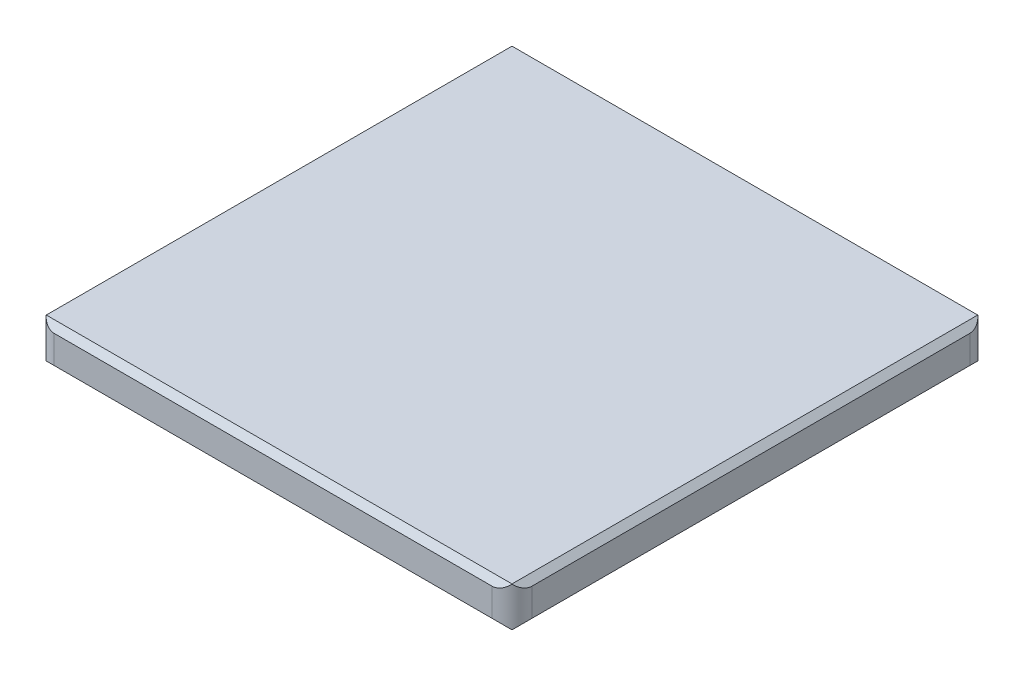
SolidWorks part; units mm, degrees
ref_plane "Front Plane" through (0, 0, 0) normal (0, 0, 1) x (1, 0, 0)
ref_plane "Top Plane" through (0, 0, 0) normal (0, 1, 0) x (1, 0, 0)
ref_plane "Right Plane" through (0, 0, 0) normal (1, 0, 0) x (0, 0, -1)
sketch "Sketch1" plane through (0, 0, 0) normal (0, 1, 0) x (1, 0, 0)
  line L1 (152.4, -152.4) -> (-152.4, -152.4)
  line L2 (152.4, -152.4) -> (152.4, 152.4)
  line L3 (152.4, 152.4) -> (-152.4, 152.4)
  line L4 (-152.4, -152.4) -> (-152.4, 152.4)
  line L5 (152.4, -152.4) -> (-152.4, 152.4) construction
  line L6 (152.4, 152.4) -> (-152.4, -152.4) construction
  point P0 (0, 0)
  dimension "D1" = 304.8
  dimension "D2" = 304.8
extrude "Boss-Extrude1" add sketch "Sketch1" along normal blind 25.4
fillet "Chamfer1" radius 3.81 4 edges at (-152.4, 0, 0) (0, 0, 152.4) (152.4, 0, 0) (0, 0, -152.4) type face fillet profile chamfer first side face at (152.4, 12.7, 0) first side face at (0, 12.7, -152.4) first side face at (-152.4, 12.7, 0) first side face at (0, 12.7, 152.4) first side face at (0, 25.4, 0) second side face at (0, 0, 0) tangent propagation no
chamfer "Chamfer2" distance 3.81 angle 45 4 edges at (0, 25.4, -152.4) (152.4, 25.4, 0) (0, 25.4, 152.4) (-152.4, 25.4, 0)
fillet "Fillet1" radius 12.7 4 edges at (152.4, 12.7, -152.4) (152.4, 12.7, 152.4) (-152.4, 12.7, 152.4) (-152.4, 12.7, -152.4)
